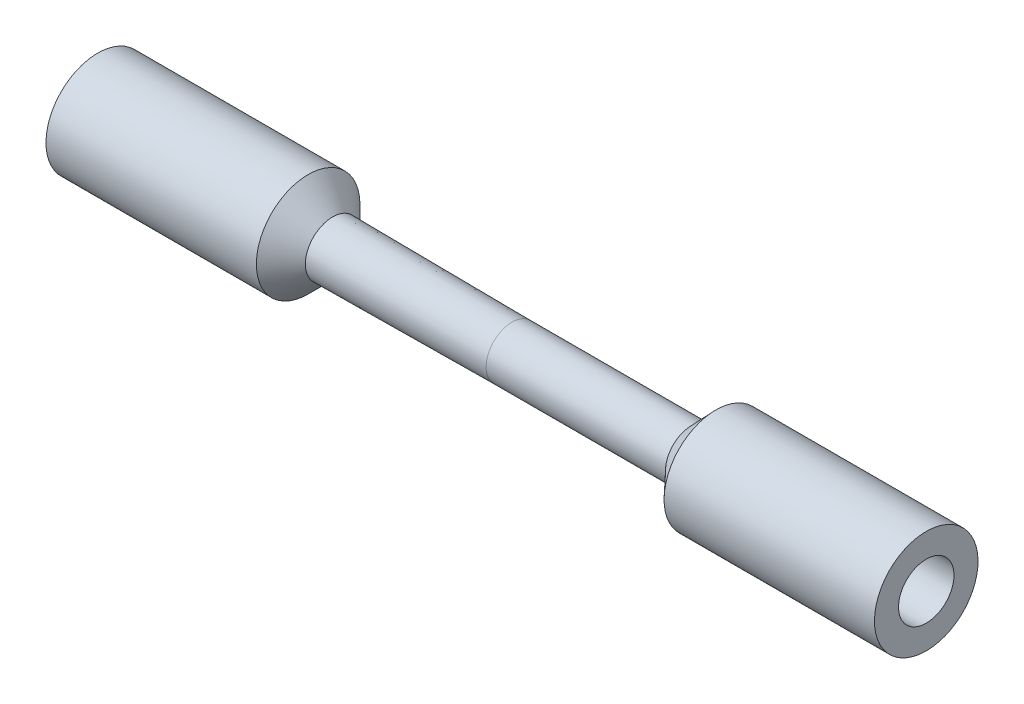
SolidWorks part; units mm, degrees
ref_plane "Front Plane" through (0, 0, 0) normal (0, 0, 1) x (1, 0, 0)
ref_plane "Top Plane" through (0, 0, 0) normal (0, 1, 0) x (1, 0, 0)
ref_plane "Right Plane" through (0, 0, 0) normal (1, 0, 0) x (0, 0, -1)
sketch "Sketch1" plane through (0, 0, 0) normal (0, 0, 1) x (1, 0, 0)
  line L0 (25.4, 1.5875) -> (14.4003, 1.5)
  line L1 (0, 0) -> (50.8, 0) construction
  line L2 (0, 0) -> (0, 3.175)
  line L3 (0, 3.175) -> (50.8, 3.175)
  line L4 (50.8, 0) -> (50.8, 3.175)
  line L5 (25.4, 3.175) -> (25.4, 0) construction
  line L6 (14.4003, 1.5) -> (12.9003, 0)
  line L7 (12.9003, 0) -> (0, 0)
  line L8 (37.8997, 0) -> (50.8, 0)
  line L9 (25.4, 1.5875) -> (36.4, 1.5875)
  line L10 (36.4, 1.5875) -> (37.8997, 0)
  point P208 (25.4, 1.5)
  dimension "D1" = 50.8
  dimension "D2" = 3.175
  dimension "D3" = 11
  dimension "D4" = 45
  dimension "D5" = 2.1213
revolve "Revolve1" add sketch "Sketch1" angle 360 about L3
sketch "Sketch4" plane through (0, 0, 0) normal (-1, 0, 0) x (0, 0, 1)
  point P0 (0, 3.175)
hole_wizard "M3 Clearance Hole1" positions "Sketch5" profile "Sketch6" hole size "M3" standard "ANSI Metric"
sketch "Sketch5" plane through (0, 0, 0) normal (-1, 0, 0) x (0, 0, 1)
  point P0 (0, 3.175)
sketch "Sketch6" plane through (0, 3.175, 0) normal (0, 1, 0) x (0, 0, 1)
  line L0 (0, 0) -> (0, 7.3715)
  line L1 (0, 7.3715) -> (1.7, 6.35)
  line L2 (1.7, 6.35) -> (1.7, 0)
  line L5 (1.7, 0) -> (0, 0)
  line L10 (0, 7.3715) -> (-1.7, 6.35) construction
  line L11 (0, -6.35) -> (0, 107.95) construction
  dimension "Hole Dia." = 3.4
  dimension "Hole Depth" = 6.35
  dimension "Drill Angle" = 118
ref_plane "Plane1" through (25.4, 0, 0) normal (-1, 0, 0) x (0, 0, 1)
mirror "Mirror1" about plane through (25.4, 0, 0) normal (-1, 0, 0) of "M3 Clearance Hole1"
equation "\"arm spacing\" = 2"
equation "\"D1@Sketch1\"=\"arm spacing\""
equation "\"D2@Sketch1\"=.25/2"
equation "\"symbol room\"= ( ( 35 / 2 ) - 6.5 )"
equation "\"D3@Sketch1\"=(\"symbol room\")/25.4"
